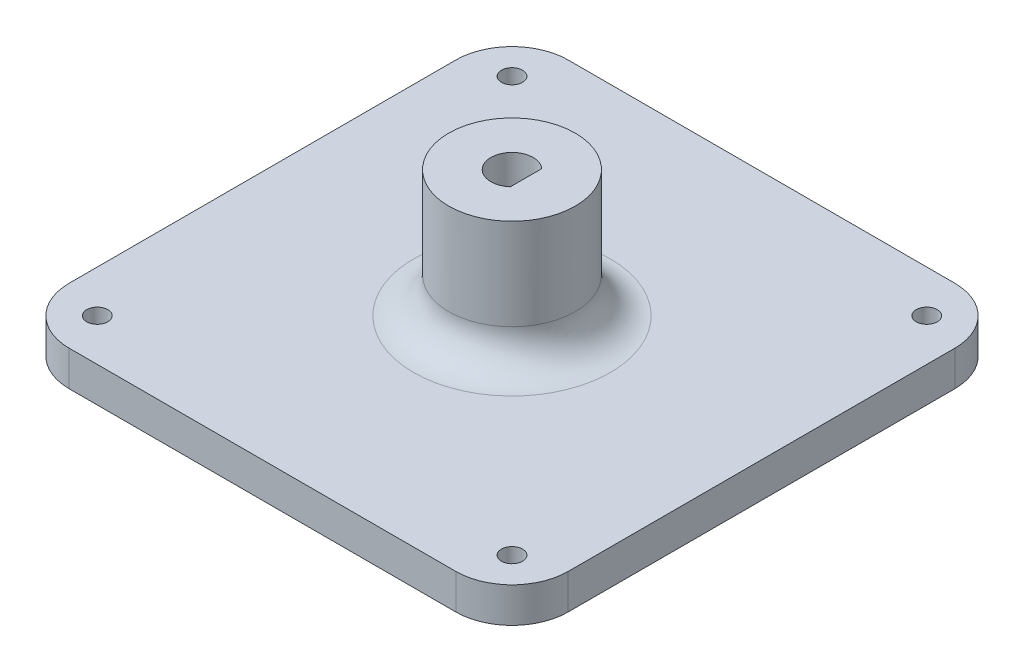
SolidWorks part; units mm, degrees
ref_plane "Front Plane" through (0, 0, 0) normal (0, 0, 1) x (1, 0, 0)
ref_plane "Top Plane" through (0, 0, 0) normal (0, 1, 0) x (1, 0, 0)
ref_plane "Right Plane" through (0, 0, 0) normal (1, 0, 0) x (0, 0, -1)
sketch "Sketch1" plane through (0, 0, 0) normal (0, 1, 0) x (1, 0, 0)
  line L1 (0, 0) -> (71, 0)
  line L2 (0, 0) -> (0, 71)
  line L3 (0, 71) -> (71, 71)
  line L4 (71, 0) -> (71, 71)
  dimension "D1" = 71
  dimension "D2" = 71
extrude "Boss-Extrude1" add sketch "Sketch1" along normal blind 5
sketch "Sketch2" plane through (0, 5, 0) normal (0, 1, 0) x (1, 0, 0)
  circle A0 centre (35.5, 35.5) radius 9
  point P0 (35.5, 35.5)
  dimension "D1" = 18
extrude "Boss-Extrude2" add sketch "Sketch2" along normal blind 18
fillet "Fillet1" radius 5 1 edges at (35.5, 5, -44.5)
sketch "Sketch3" plane through (0, 23, 0) normal (0, 1, 0) x (1, 0, 0)
  line L1 (37.5, 38.5) -> (40.6932, 38.5)
  line L2 (37.5, 38.5) -> (37.5, 32.5)
  line L3 (37.5, 32.5) -> (40.6932, 32.5)
  line L4 (40.6932, 38.5) -> (40.6932, 32.5)
  circle A0 centre (35.5, 35.5) radius 3
  point P0 (35.5, 35.5)
  dimension "D1" = 6
  dimension "D2" = 2
extrude "Cut-Extrude1" cut sketch "Sketch3" against normal blind 16 contours L2 A0 region at (35.204, 23, -35.5)
fillet "Fillet2" radius 8 4 edges at (0, 2.5, 0) (71, 2.5, 0) (71, 2.5, -71) (0, 2.5, -71)
sketch "Sketch4" plane through (0, 5, 0) normal (0, 1, 0) x (1, 0, 0)
  line L0 (63, 71) -> (8, 71) construction
  line L1 (71, 8) -> (71, 63) construction
  line L2 (8, 0) -> (63, 0) construction
  line L3 (0, 63) -> (0, 8) construction
  circle A0 centre (65, 65) radius 1.5
  circle A1 centre (65, 6) radius 1.5
  circle A2 centre (6, 6) radius 1.5
  circle A3 centre (6, 65) radius 1.5
  dimension "D1" = 3
  dimension "D6" = 3
  dimension "D9" = 3
  dimension "D12" = 3
  dimension "D2" = 6
  dimension "D3" = 6
  dimension "D4" = 6
  dimension "D5" = 6
  dimension "D7" = 6
  dimension "D8" = 6
  dimension "D10" = 6
  dimension "D11" = 6
extrude "Cut-Extrude2" cut sketch "Sketch4" against normal through all
sketch "Sketch5" plane through (0, 0, 0) normal (0, -1, 0) x (-1, 0, 0)
  line L1 (-43.5829, 35.5) -> (-39.5415, 28.5)
  line L2 (-39.5415, 28.5) -> (-31.4585, 28.5)
  line L3 (-31.4585, 28.5) -> (-27.4171, 35.5)
  line L4 (-27.4171, 35.5) -> (-31.4585, 42.5)
  line L5 (-31.4585, 42.5) -> (-39.5415, 42.5)
  line L6 (-39.5415, 42.5) -> (-43.5829, 35.5)
  circle A0 centre (-35.5, 35.5) radius 7 construction
  point P0 (-35.5, 35.5)
  dimension "D1" = 14
extrude "Cut-Extrude3" cut sketch "Sketch5" against normal blind 10
